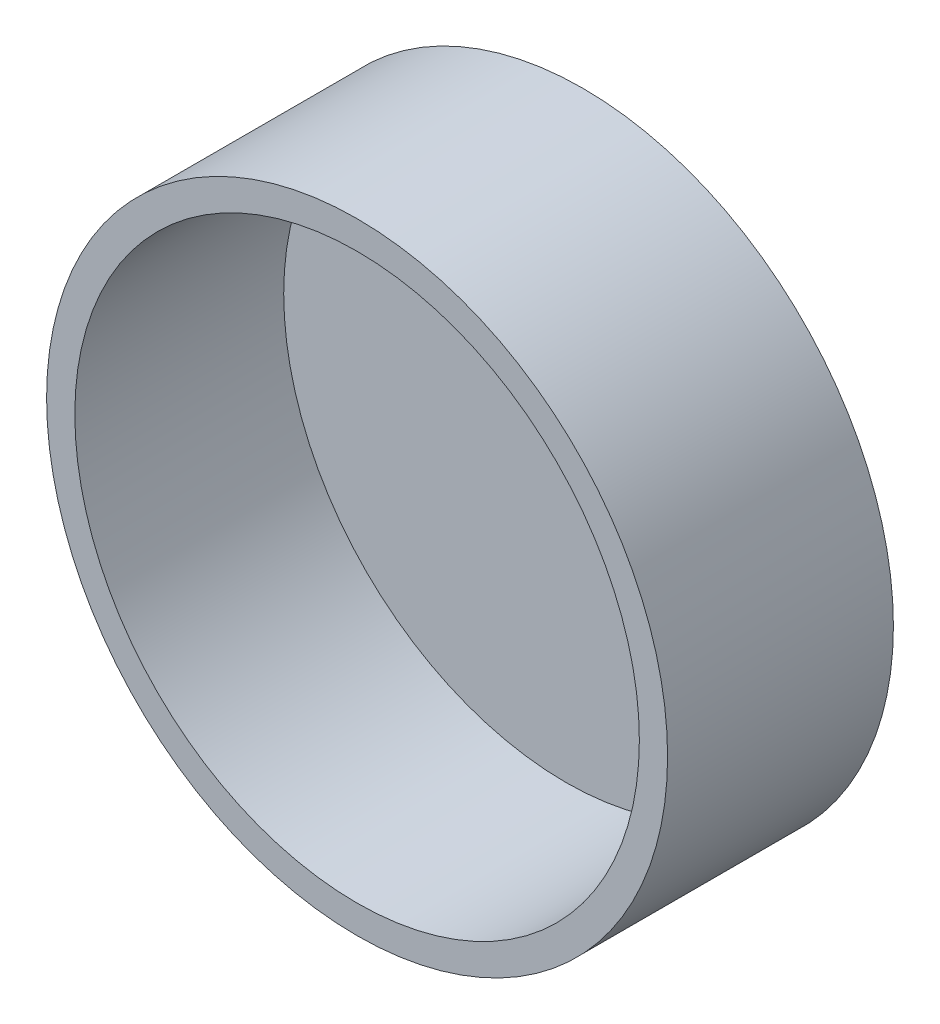
SolidWorks part; units mm, degrees
ref_plane "Front Plane" through (0, 0, 0) normal (0, 0, 1) x (1, 0, 0)
ref_plane "Top Plane" through (0, 0, 0) normal (0, 1, 0) x (1, 0, 0)
ref_plane "Right Plane" through (0, 0, 0) normal (1, 0, 0) x (0, 0, -1)
sketch "Sketch1" plane through (0, 0, 0) normal (0, 0, 1) x (1, 0, 0)
  line L0 (0, 65) -> (50, 65)
  line L1 (0, 65) -> (-50, 65)
  circle A0 centre (0, 0) radius 100
  circle A1 centre (0, 0) radius 110
  circle A3 centre (0, 65) radius 14
  circle A6 centre (0, 65) radius 17
  circle A9 centre (-41.1218, 65) radius 6.7
  circle A10 centre (41.1218, 65) radius 6.9
  circle A11 centre (-41.1218, 65) radius 10
  circle A12 centre (41.1218, 65) radius 10
  circle A13 centre (0, 65) radius 10.75
  circle A14 centre (-41.1218, 65) radius 3
  circle A15 centre (-64.4446, 54.4199) radius 2.25
  circle A16 centre (-64.4446, 54.4199) radius 5
extrude "Boss-Extrude1" add sketch "Sketch1" along normal blind 6 contours A0 A12 A6 A11 | L1 A6 L0 A3 | L0 A6 L1 A3 | A12 A10 | A11 A9 | A16 A15 region at (0, 79.3801, 0) region at (15.5, 64.6199, 0) region at (41.1218, 74.7172, 0) region at (-50.839, 65, 0) region at (0.1698, -3.4941, 0) region at (-69.3032, 54.4199, 0)
extrude "Boss-Extrude2" add sketch "Sketch1<3>" along normal blind 80 contours A1 A0 region at (-106.8887, 0, 0)
sketch "Sketch1<3>" plane through (0, 0, 0) normal (0, 0, 1) x (1, 0, 0) same geometry as "Sketch1"
extrude "Boss-Extrude3" add sketch "Sketch1<10>" against normal blind 5 contours A12 A10 | L0 A6 L1 A3 | L1 A6 L0 A3 | A11 A9 | A14 L1 A9 | A14 L1 A9 | A13 L0 A3 L1 | A13 L1 A3 L0 | A16 A15 region at (0, 76.063, 0) region at (12.375, 64.687, 0) region at (0, 79.3801, 0) region at (15.5, 64.6199, 0) region at (41.1218, 74.7172, 0) region at (-41.1218, 61.7626, 0) region at (-41.1218, 68.2374, 0) region at (-50.839, 65, 0) region at (-69.3032, 54.4199, 0)
sketch "Sketch1<10>" plane through (0, 0, 0) normal (0, 0, 1) x (1, 0, 0) same geometry as "Sketch1"
